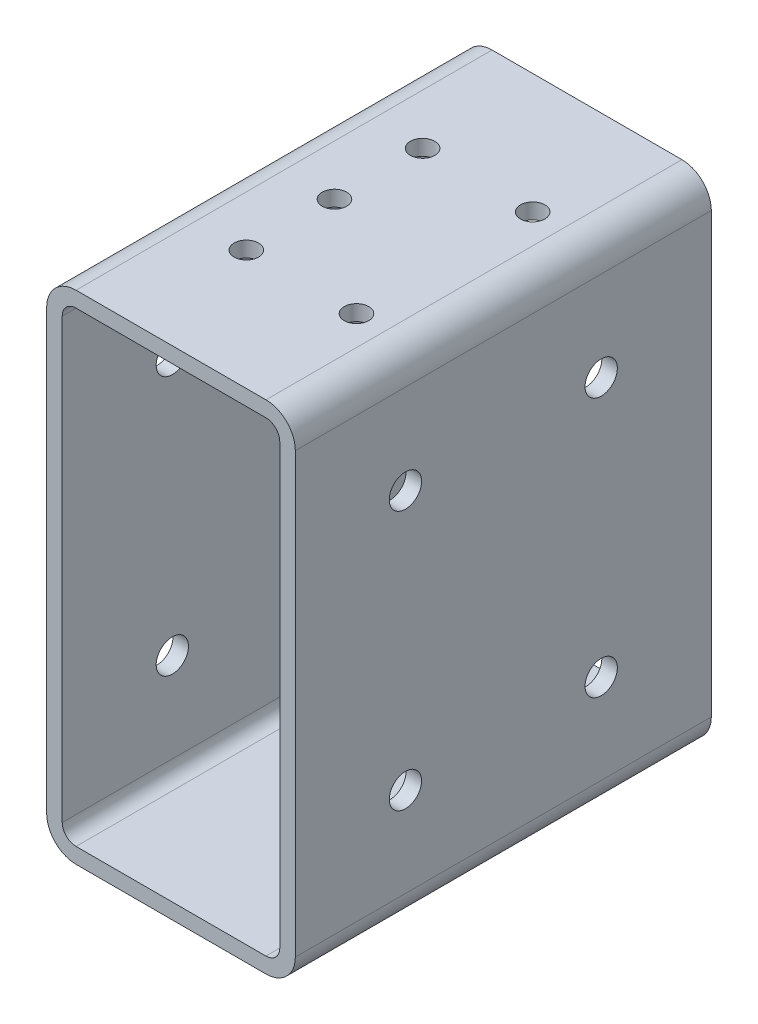
SolidWorks part; units mm, degrees
material "Plain Carbon Steel"
ref_plane "Front Plane" through (0, 0, 0) normal (0, 0, 1) x (1, 0, 0)
ref_plane "Top Plane" through (0, 0, 0) normal (0, 1, 0) x (1, 0, 0)
ref_plane "Right Plane" through (0, 0, 0) normal (1, 0, 0) x (0, 0, -1)
sketch "Sketch1" plane through (0, 0, 0) normal (0, 0, 1) x (1, 0, 0)
  line L0 (19.4, 47.625) -> (-19.4, 47.625)
  line L1 (19.4, -50.8) -> (-19.4, -50.8)
  line L2 (25.4, -44.8) -> (25.4, 44.8)
  line L3 (19.4, 50.8) -> (-19.4, 50.8)
  line L4 (-25.4, -44.8) -> (-25.4, 44.8)
  line L5 (25.4, -50.8) -> (-25.4, 50.8) construction
  line L6 (25.4, 50.8) -> (-25.4, -50.8) construction
  line L7 (-22.225, -44.8) -> (-22.225, 44.8)
  line L8 (19.4, -47.625) -> (-19.4, -47.625)
  line L9 (22.225, -44.8) -> (22.225, 44.8)
  arc A0 (-19.4, -50.8) -> (-25.4, -44.8) centre (-19.4, -44.8) cw
  arc A1 (19.4, -50.8) -> (25.4, -44.8) centre (19.4, -44.8) ccw
  arc A2 (25.4, 44.8) -> (19.4, 50.8) centre (19.4, 44.8) ccw
  arc A3 (-19.4, 50.8) -> (-25.4, 44.8) centre (-19.4, 44.8) ccw
  arc A4 (-19.4, 47.625) -> (-22.225, 44.8) centre (-19.4, 44.8) ccw
  arc A5 (-19.4, -47.625) -> (-22.225, -44.8) centre (-19.4, -44.8) cw
  arc A6 (19.4, -47.625) -> (22.225, -44.8) centre (19.4, -44.8) ccw
  arc A7 (22.225, 44.8) -> (19.4, 47.625) centre (19.4, 44.8) ccw
  point P0 (0, 0)
  dimension "D1" = 6
  dimension "D3" = 101.6
  dimension "D4" = 50.8
  dimension "D2" = 3.175
extrude "Boss-Extrude1" add sketch "Sketch1" along normal mid plane 85
sketch "Sketch2" plane through (25.4, 0, 0) normal (1, 0, 0) x (0, 0, -1)
  line L1 (20, 26.5) -> (-20, 26.5) construction
  line L2 (20, 26.5) -> (20, -26.5) construction
  line L3 (20, -26.5) -> (-20, -26.5) construction
  line L4 (-20, 26.5) -> (-20, -26.5) construction
  line L5 (20, 26.5) -> (-20, -26.5) construction
  line L6 (20, -26.5) -> (-20, 26.5) construction
  circle A0 centre (-20, 26.5) radius 3.3
  circle A1 centre (20, 26.5) radius 3.3
  circle A2 centre (20, -26.5) radius 3.3
  circle A3 centre (-20, -26.5) radius 3.3
  point P0 (0, 0)
  dimension "D3" = 6.6
  dimension "D1" = 53
  dimension "D2" = 40
extrude "Cut-Extrude1" cut sketch "Sketch2" against normal through all
sketch "Sketch3" plane through (0, 50.8, 0) normal (0, 1, 0) x (1, 0, 0)
  line L0 (-24.6642, 0) -> (5.453, 0) construction
  line L1 (-9.1, 18) -> (-9.1, -18) construction
  line L2 (-9.1, 18) -> (13.4, 18) construction
  line L3 (13.4, 18) -> (13.4, -18) construction
  line L4 (25.4, -42.5) -> (25.4, 42.5) construction
  circle A0 centre (-9.1, 18) radius 2.5
  circle A1 centre (-9.1, 0) radius 2.5
  circle A2 centre (-9.1, -18) radius 2.5
  circle A3 centre (13.4, 18) radius 2.5
  circle A4 centre (13.4, -18) radius 2.5
  point P5 (-9.1, 0)
  dimension "D2" = 5
  dimension "D1" = 36
  dimension "D3" = 22.5
  dimension "D4" = 12
extrude "Cut-Extrude2" cut sketch "Sketch3" against normal up to surface (3.175 mm away) up to face at (0, 47.625, 0)
equation "\"M5_tap\"=4.2mm       ' Below you can do mesurements as follows: cm, mm, ft, in, m, "
equation "\"M5_clearence\"=5.5mm"
equation "\"M6_tap\"=5mm"
equation "\"M6_clearence\"=6.6mm"
equation "\"work_area_width\"=1100mm"
equation "\"work_area_depth\"=900mm"
equation "\"D3@Sketch1\"=\"steel_zbox_width\""
equation "\"D4@Sketch1\"=\"steel_zbox_height\""
equation "\"D1@Sketch1\"=\"steel_zbox_radius\""
equation "\"D2@Sketch1\"=\"steel_zbox_wall_thickness\""
equation "\"D1@Boss-Extrude1\"=\"length\""
equation "\"steel_base_width\"=3in "
equation "\"steel_base_height\"=2in"
equation "\"steel_base_wall_thickness\"=0.125in"
equation "\"steel_base_radius\"=6mm"
equation "\"steel_sides_width\"=3in     'this tube is rotated so flip width/height"
equation "\"steel_sides_height\"=2in    'this tube is rotated so flip width/height"
equation "\"steel_sides_wall_thickness\"=0.125in"
equation "\"steel_sides_radius\"=6mm"
equation "\"steel_gantry_width\"=4in    'this tube is rotated so flip width/height"
equation "\"steel_gantry_height\"=3in    'this tube is rotated so flip width/height"
equation "\"steel_gantry_wall_thickness\"=0.125in"
equation "\"steel_gantry_radius\"=6mm"
equation "\"D3@Sketch2\"=\"M6_clearence\""
equation "\"D2@Sketch3\"=\"M6_tap\""
equation "\"steel_rollers_width\"=3in"
equation "\"steel_rollers_height\"=2in    'keep as low as possible as this increases how big plastic parts are"
equation "\"steel_rollers_wall_thickness\"=0.125in"
equation "\"steel_rollers_radius\"=6mm"
equation "\"steel_zbox_width\"=4in     'if the gantry height (rotated) is too thick, a wider zbox is necessary"
equation "\"steel_zbox_height\"=2in     'hole patteren changes as the zbox and gantry height (rotated) changes."
equation "\"steel_zbox_wall_thickness\"=0.125in"
equation "\"steel_zbox_radius\"=6mm"
equation "\"D4@Sketch3\"=\"steel_zbox_radius\" * 2"
equation "\"length\"= 100mm - 7.5 * 2"
